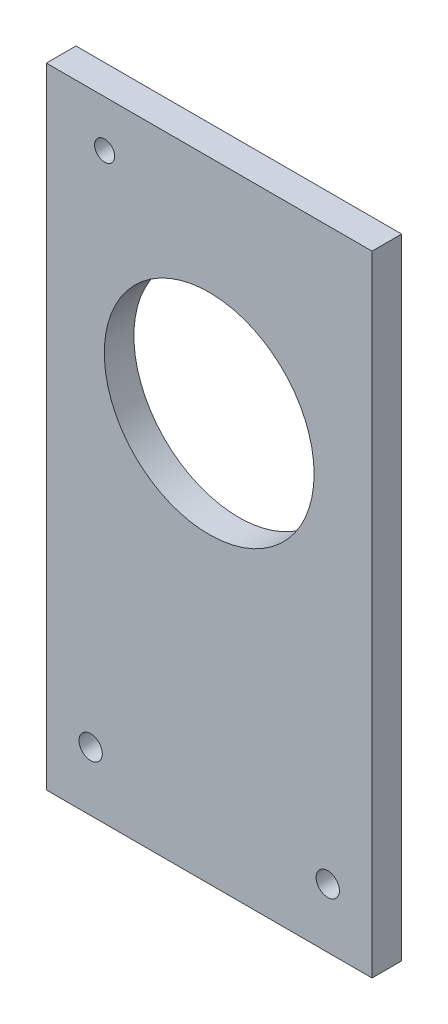
SolidWorks part; units mm, degrees
ref_plane "Front Plane" through (0, 0, 0) normal (0, 0, 1) x (1, 0, 0)
ref_plane "Top Plane" through (0, 0, 0) normal (0, 1, 0) x (1, 0, 0)
ref_plane "Right Plane" through (0, 0, 0) normal (1, 0, 0) x (0, 0, -1)
sketch "Sketch2" plane through (0, 0, 0) normal (0, 0, 1) x (1, 0, 0)
  line L0 (-55, 77.9) -> (55, 77.9) construction
  line L1 (-34.925, 0) -> (34.925, 0)
  line L2 (-34.925, 0) -> (-34.925, 87.4)
  line L3 (-34.925, 87.4) -> (34.925, 87.4) construction
  line L4 (34.925, 0) -> (34.925, 87.4)
  line L5 (0, 77.9) -> (0, 0) construction
  line L6 (0, 77.9) -> (0, 87.4) construction
  line L7 (-34.925, 25.4) -> (34.925, 25.4) construction
  line L10 (34.925, 119.9) -> (-34.925, 119.9) construction
  line L11 (34.925, 87.4) -> (34.925, 119.9)
  line L12 (34.925, 119.9) -> (-34.925, 119.9) construction
  line L13 (-34.925, 119.9) -> (-34.925, 87.4)
  line L14 (34.925, 119.9) -> (34.925, 135)
  line L15 (34.925, 135) -> (-34.925, 135)
  line L16 (-34.925, 119.9) -> (-34.925, 135)
  circle A0 centre (-55, 77.9) radius 3 construction
  circle A1 centre (55, 77.9) radius 3 construction
  circle A2 centre (-55, 77.9) radius 15 construction
  circle A3 centre (55, 77.9) radius 15 construction
  circle A6 centre (0, 87.4) radius 22.5
  circle A7 centre (-55, 77.9) radius 15.6 construction
  point P6 (0, 0)
  dimension "D1" = 6
  dimension "D2" = 30
  dimension "D5" = 45
  dimension "D9" = 135
  dimension "D3" = 110
  dimension "D4" = 9.5
  dimension "D6" = 69.85
  dimension "D7" = 36.9
  dimension "D8" = 32.5
  dimension "D10" = 25.4
  dimension "D11" = 0.6
extrude "Boss-Extrude1" add sketch "Sketch2" along normal mid plane 6.35
sketch "Sketch3" plane through (0, 0, 3.175) normal (0, 0, 1) x (1, 0, 0)
  line L0 (34.925, 135) -> (-34.925, 135) construction
  line L1 (-34.925, 0) -> (-25.425, 0) construction
  line L2 (-34.925, 0) -> (-34.925, 12.7) construction
  line L3 (-34.925, 12.7) -> (-25.425, 12.7) construction
  line L4 (-25.425, 0) -> (-25.425, 12.7) construction
  line L5 (34.925, 0) -> (25.425, 0) construction
  line L6 (34.925, 0) -> (34.925, 12.7) construction
  line L7 (34.925, 12.7) -> (25.425, 12.7) construction
  line L8 (25.425, 0) -> (25.425, 12.7) construction
  line L9 (-34.925, 135) -> (-34.925, 0) construction
  circle A0 centre (-25.425, 12.7) radius 2.5
  circle A1 centre (25.425, 12.7) radius 2.5
  circle A2 centre (-22.425, 125) radius 2.15
  point P12 (0, 0)
  point P19 (-32.2269, 128.201)
  dimension "D1" = 12.7
  dimension "D2" = 5
  dimension "D4" = 4.3
  dimension "D5" = 10
  dimension "D3" = 9.5
  dimension "D6" = 12.5
extrude "Cut-Extrude1" cut sketch "Sketch3" against normal through all both and the other way through all
